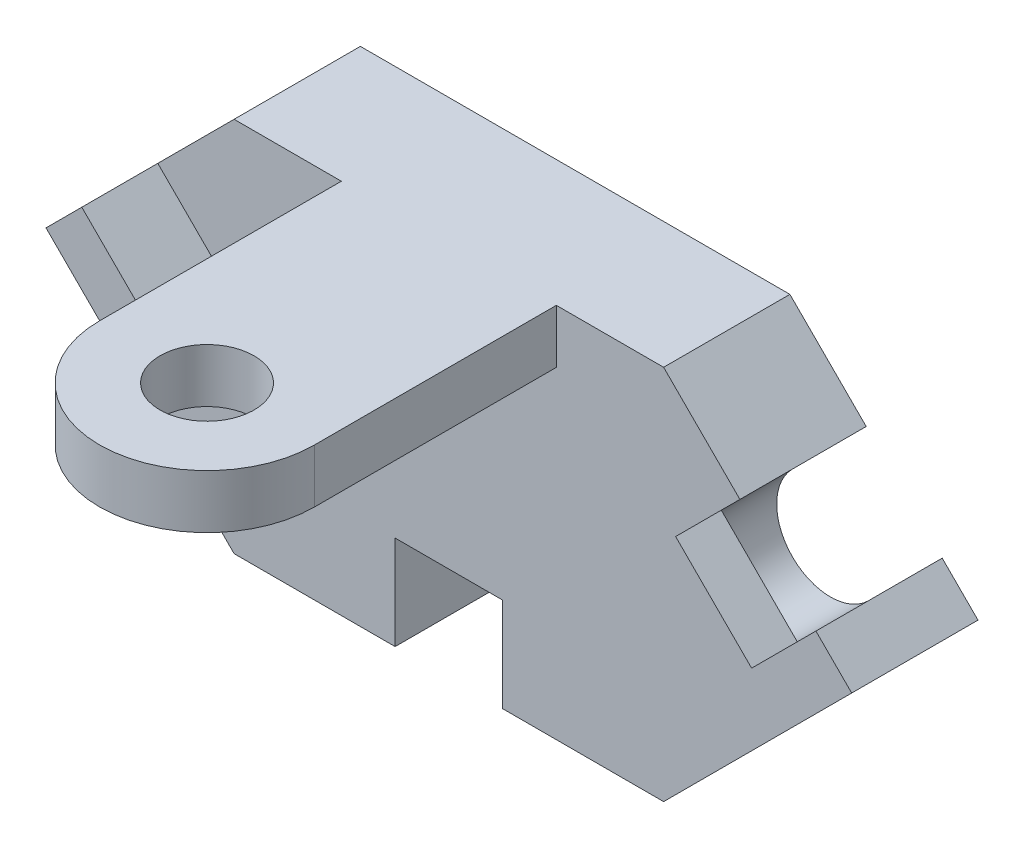
SolidWorks part; units mm, degrees
ref_plane "Plano frontal" through (0, 0, 0) normal (0, 0, 1) x (1, 0, 0)
ref_plane "Plano superior" through (0, 0, 0) normal (0, 1, 0) x (1, 0, 0)
ref_plane "Plano direito" through (0, 0, 0) normal (1, 0, 0) x (0, 0, -1)
sketch "Esboço1" plane through (0, 0, 0) normal (0, 0, 1) x (1, 0, 0)
  line L0 (-7.9929, 7) -> (-10.8322, 4.1607)
  line L1 (-14.9929, 0) -> (-7.9929, -7)
  line L2 (-7.9929, -7) -> (-2, -7)
  line L3 (7.9929, -7) -> (14.9929, 0)
  line L4 (14.9929, 0) -> (13.6607, 1.3322)
  line L5 (7.9929, 7) -> (-7.9929, 7)
  line L6 (0, 7) -> (0, -7) construction
  line L7 (-9.5, 0) -> (-12.2464, 2.7464) construction
  line L8 (9.5, 0) -> (12.3339, 2.8339) construction
  line L9 (-8.0858, 1.4142) -> (-10.8322, 4.1607)
  line L10 (10.9142, -1.4142) -> (13.6607, 1.3322)
  line L11 (-10.9142, -1.4142) -> (-13.6607, 1.3322)
  line L12 (8.0858, 1.4142) -> (10.8322, 4.1607)
  line L13 (-13.6607, 1.3322) -> (-14.9929, 0)
  line L14 (10.8322, 4.1607) -> (7.9929, 7)
  line L15 (-2, -3) -> (-2, -7)
  line L16 (2, -3) -> (2, -7)
  line L17 (2, -7) -> (7.9929, -7)
  arc A0 (-10.9142, -1.4142) -> (-8.0858, 1.4142) centre (-9.5, 0) ccw
  arc A1 (8.0858, 1.4142) -> (10.9142, -1.4142) centre (9.5, 0) ccw
  arc A2 (2, -3) -> (-2, -3) centre (0, -3) ccw
  dimension "D5" = 3
  dimension "D4" = 2
  dimension "D1" = 29.9858
  dimension "D2" = 14
  dimension "D3" = 19
extrude "Ressalto-extrusão1" add sketch "Esboço1" along normal blind 3
sketch "Esboço2" plane through (0, 0, 3) normal (0, 0, 1) x (1, 0, 0)
  line L0 (-11.2678, -1.0607) -> (-8.4393, 1.7678)
  line L1 (0, 7) -> (0, -7) construction
  line L2 (11.2678, -1.0607) -> (8.4393, 1.7678)
  line L3 (11.2678, -1.0607) -> (13.6607, 1.3322)
  line L4 (10.8322, 4.1607) -> (8.4393, 1.7678)
  line L5 (2, -3.5) -> (-2, -3.5)
  line L12 (7.9929, 7) -> (-7.9929, 7)
  line L13 (-7.9929, 7) -> (-10.8322, 4.1607)
  line L14 (-10.8322, 4.1607) -> (-8.0858, 1.4142)
  line L15 (-10.9142, -1.4142) -> (-13.6607, 1.3322)
  line L16 (-13.6607, 1.3322) -> (-14.9929, 0)
  line L17 (-14.9929, 0) -> (-7.9929, -7)
  line L18 (-7.9929, -7) -> (-2, -7)
  line L19 (7.9929, -7) -> (14.9929, 0)
  line L20 (14.9929, 0) -> (13.6607, 1.3322)
  line L21 (13.6607, 1.3322) -> (10.9142, -1.4142)
  line L22 (8.0858, 1.4142) -> (10.8322, 4.1607)
  line L23 (10.8322, 4.1607) -> (7.9929, 7)
  line L24 (7.9929, 7) -> (-7.9929, 7)
  line L25 (-7.9929, 7) -> (-10.8322, 4.1607)
  line L26 (-10.8322, 4.1607) -> (-8.4393, 1.7678)
  line L27 (-11.2678, -1.0607) -> (-13.6607, 1.3322)
  line L28 (-13.6607, 1.3322) -> (-14.9929, 0)
  line L29 (-14.9929, 0) -> (-7.9929, -7)
  line L30 (-7.9929, -7) -> (-2, -7)
  line L31 (7.9929, -7) -> (14.9929, 0)
  line L32 (14.9929, 0) -> (13.6607, 1.3322)
  line L35 (10.8322, 4.1607) -> (7.9929, 7)
  line L42 (-2, -7) -> (-2, -3)
  line L43 (-2, -7) -> (-2, -3.5)
  line L44 (2, -3) -> (2, -7)
  line L45 (2, -3.5) -> (2, -7)
  line L46 (2, -7) -> (7.9929, -7)
  line L47 (2, -7) -> (7.9929, -7)
  arc A2 (-10.9142, -1.4142) -> (-8.0858, 1.4142) centre (-9.5, 0) ccw
  arc A3 (8.0858, 1.4142) -> (10.9142, -1.4142) centre (9.5, 0) ccw
  arc A7 (2, -3) -> (-2, -3) centre (0, -3) ccw
  dimension "D2" = 0.5
  dimension "D3" = 0.5
  dimension "D1" = 0
extrude "Ressalto-extrusão2" add sketch "Esboço2" along normal blind 1.7
sketch "Esboço3" plane through (0, 7, 0) normal (0, 1, 0) x (1, 0, 0)
  line L1 (-7.9929, -2.35) -> (7.9929, -2.35) construction
  line L2 (7.9929, 0) -> (-7.9929, 0) construction
  line L3 (7.9929, -4.7) -> (-7.9929, -4.7) construction
  line L7 (-7.9929, -4.7) -> (-7.9929, 0) construction
  line L9 (7.9929, -4.7) -> (7.9929, 0) construction
  line L10 (-4, -4.7) -> (4, -13.7) construction
  line L11 (-4, -13.7) -> (4, -4.7) construction
  line L12 (4, -13.7) -> (4, -4.7)
  line L13 (-4, -4.7) -> (4, -4.7)
  line L14 (-4, -13.7) -> (-4, -4.7)
  circle A2 centre (0, -13.7) radius 1.75
  arc A3 (4, -13.7) -> (-4, -13.7) centre (0, -13.7) cw
  point P25 (0, -9.2)
  dimension "D3" = 13.7
  dimension "D1" = 4
  dimension "D2" = 3.5
  dimension "D4" = 8
extrude "Ressalto-extrusão3" add sketch "Esboço3" against normal blind 2
equation "\"D3@Esboço2\"=\"D2@Esboço2\""
